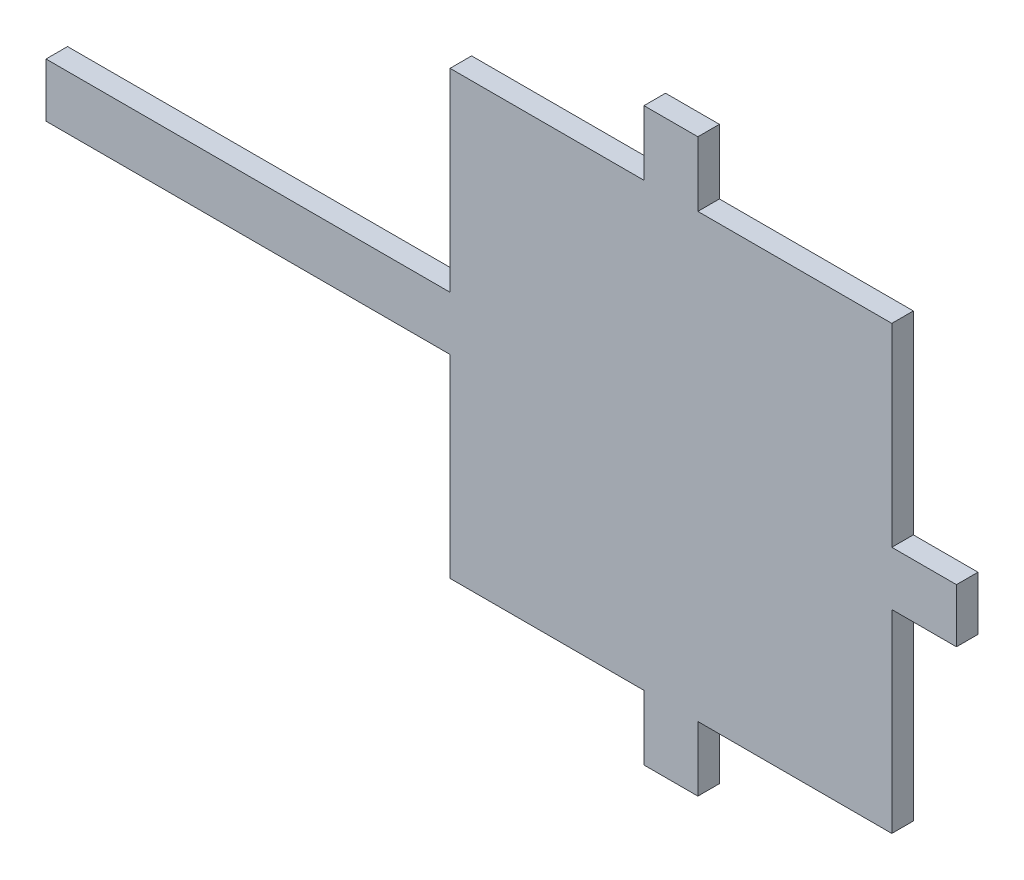
SolidWorks part; units mm, degrees
ref_plane "Front Plane" through (0, 0, 0) normal (0, 0, 1) x (1, 0, 0)
ref_plane "Top Plane" through (0, 0, 0) normal (0, 1, 0) x (1, 0, 0)
ref_plane "Right Plane" through (0, 0, 0) normal (1, 0, 0) x (0, 0, -1)
sketch "Sketch1" plane through (0, 0, 0) normal (0, 0, 1) x (1, 0, 0)
  line L1 (-41, -41) -> (41, -41)
  line L2 (-41, -41) -> (-41, 41)
  line L3 (-41, 41) -> (41, 41)
  line L4 (41, -41) -> (41, 41)
  line L5 (-41, -41) -> (41, 41) construction
  line L6 (-41, 41) -> (41, -41) construction
  point P0 (0, 0)
  dimension "D1" = 82
  dimension "D2" = 82
extrude "Boss-Extrude3" add sketch "Sketch1" along normal blind 4
ref_plane "Plane3" through (0, 0, 0) normal (1, 0, 0) x (0, 0, -1)
ref_plane "Plane4" through (0, 0, 0) normal (0, -1, 0) x (-1, 0, 0)
sketch "Sketch6" plane through (0, 41, 0) normal (0, 1, 0) x (1, 0, 0)
  line L0 (0, 0) -> (0, -4) construction
  line L1 (41, 0) -> (-41, 0) construction
  line L2 (41, -4) -> (-41, -4) construction
  line L4 (5, 0) -> (-5, 0)
  line L5 (5, 0) -> (5, -4)
  line L6 (5, -4) -> (-5, -4)
  line L7 (-5, 0) -> (-5, -4)
  line L8 (5, 0) -> (-5, -4) construction
  line L9 (5, -4) -> (-5, 0) construction
  point P6 (0, -2)
extrude "Boss-Extrude4" add sketch "Sketch6" along normal blind 12
ref_axis "Axis1" through (0, 0, 4.2) along (0, 0, -1)
pattern_circular "CirPattern1" count 3 every 90 about axis through (0, 0, 4.2) along (0, 0, -1) of "Boss-Extrude4"
sketch "Sketch8" plane through (-41, 0, 0) normal (-1, 0, 0) x (0, 0, 1)
  line L0 (0, 0) -> (4, 0) construction
  line L1 (0, 41) -> (0, -41) construction
  line L2 (4, 41) -> (4, -41) construction
  line L4 (0, 5) -> (4, 5)
  line L5 (0, 5) -> (0, -5)
  line L6 (0, -5) -> (4, -5)
  line L7 (4, 5) -> (4, -5)
  line L8 (0, 5) -> (4, -5) construction
  line L9 (0, -5) -> (4, 5) construction
  point P6 (2, 0)
extrude "Boss-Extrude5" add sketch "Sketch8" along normal blind 75
sketch "Sketch9" plane through (0, 0, 4) normal (0, 0, 1) x (1, 0, 0)
  line L0 (-116, 0) -> (-83, 0) construction
  line L1 (-116, -5) -> (-116, 5) construction
  line L3 (-79.1637, 3.596) -> (-86.8363, 3.596)
  line L4 (-79.1637, 3.596) -> (-79.1637, -3.596)
  line L5 (-79.1637, -3.596) -> (-86.8363, -3.596)
  line L6 (-86.8363, 3.596) -> (-86.8363, -3.596)
  line L7 (-79.1637, 3.596) -> (-86.8363, -3.596) construction
  line L8 (-79.1637, -3.596) -> (-86.8363, 3.596) construction
sketch "Sketch12" plane through (0, 5, 0) normal (0, 1, 0) x (1, 0, 0)
  line L0 (-116, -4) -> (-116, 0) construction
  line L2 (-116, -4) -> (-41, -4) construction
  line L3 (-77.6666, 0) -> (-88.3334, 0)
  line L4 (-77.6666, 0) -> (-77.6666, -4)
  line L5 (-77.6666, -4) -> (-88.3334, -4)
  line L6 (-88.3334, 0) -> (-88.3334, -4)
  line L7 (-77.6666, 0) -> (-88.3334, -4) construction
  line L8 (-77.6666, -4) -> (-88.3334, 0) construction
  line L9 (-83, -2) -> (-116, -2) construction
